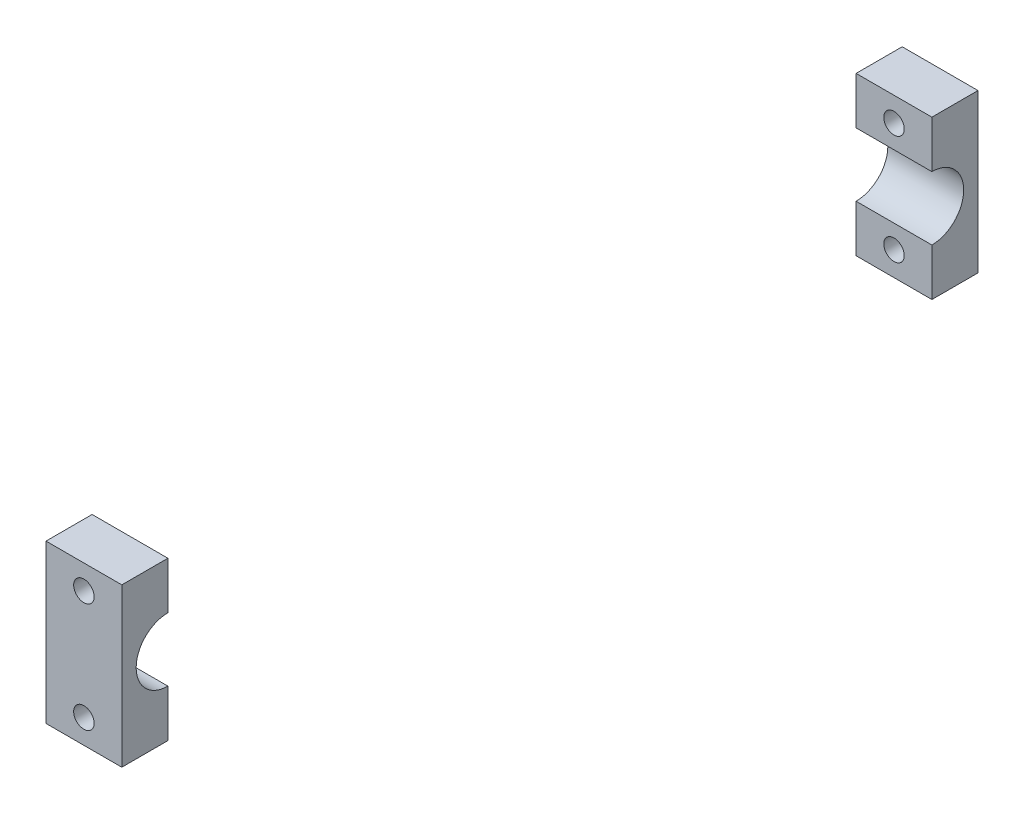
SolidWorks part; units mm, degrees
material "ABS"
ref_plane "Front Plane" through (0, 0, 0) normal (0, 0, 1) x (1, 0, 0)
ref_plane "Top Plane" through (0, 0, 0) normal (0, 1, 0) x (1, 0, 0)
ref_plane "Right Plane" through (0, 0, 0) normal (1, 0, 0) x (0, 0, -1)
sketch "Sketch2" plane through (0, 0, 0) normal (1, 0, 0) x (0, 0, -1)
  line L1 (-90, -4.5) -> (90, -4.5)
  line L2 (-90, -4.5) -> (-90, 4.5)
  line L3 (-90, 4.5) -> (90, 4.5)
  line L4 (90, -4.5) -> (90, 4.5)
  line L5 (-90, -4.5) -> (90, 4.5) construction
  line L6 (-90, 4.5) -> (90, -4.5) construction
  point P0 (0, 0)
  dimension "D1" = 9
  dimension "D2" = 180
extrude "Boss-Extrude1" add sketch "Sketch2" along normal blind 14.8
sketch "Sketch3" plane through (14.8, 0, 0) normal (1, 0, 0) x (0, 0, -1)
  line L0 (-90, -4.5) -> (90, -4.5) construction
  line L1 (-74.579, -4.5) -> (74.579, -4.5) construction
  line L7 (90, -4.5) -> (90, 4.5)
  line L8 (90, 4.5) -> (-90, 4.5)
  line L9 (-90, 4.5) -> (-90, -4.5)
  line L10 (-90, -4.5) -> (90, -4.5)
  line L11 (90, -4.5) -> (90, 4.5)
  line L12 (90, 4.5) -> (-90, 4.5)
  line L13 (-90, 4.5) -> (-90, -4.5)
  arc A0 (-68.379, -4.5) -> (-80.779, -4.5) centre (-74.579, -4.5) ccw
  arc A1 (80.779, -4.5) -> (68.379, -4.5) centre (74.579, -4.5) ccw
  point P10 (0, -4.5)
  dimension "D1" = 6.2
  dimension "D2" = 149.158
  dimension "D4" = 0
extrude "Bar Holes" [suppressed] cut sketch "Sketch3" against normal through all
sketch "Sketch6" [suppressed] plane through (0, 4.5, 0) normal (0, 1, 0) x (1, 0, 0)
  line L0 (7.4, 63.879) -> (7.4, -63.879) construction
  line L1 (14.8, 90) -> (0, 90) construction
  line L2 (14.8, -90) -> (0, -90) construction
  line L3 (0, -68.379) -> (14.8, -68.379) construction
  line L4 (0, -80.779) -> (14.8, -80.779) construction
  line L5 (-32.5661, 0) -> (77.6197, 0) construction
  circle A0 centre (7.4, 63.879) radius 2
  circle A1 centre (7.4, -63.879) radius 2
  circle A2 centre (7.4, -85.279) radius 2
  circle A3 centre (7.4, 85.279) radius 2
  circle A4 centre (7.4, -32.5) radius 3.5 construction
  circle A5 centre (7.4, 32.5) radius 3.5 construction
  point P4 (7.4, 0)
  point P8 (7.4, 90)
  point P17 (7.4, -90)
  dimension "D1" = 4
  dimension "D2" = 4
  dimension "D5" = 4
  dimension "D6" = 4
  dimension "D10" = 7
  dimension "D11" = 7
  dimension "D7" = 32.5
  dimension "D3" = 4.5
  dimension "D4" = 4.5
  dimension "D8" = 4.5
  dimension "D9" = 32.5
extrude "Bolt Holes" [suppressed] cut sketch "Sketch6" against normal through all
sketch "Sketch7" plane through (14.8, 0, 0) normal (1, 0, 0) x (0, 0, -1)
  line L0 (-90, -4.5) -> (90, -4.5) construction
  line L1 (-45, -4.5) -> (45, -4.5)
  line L2 (-45, -4.5) -> (-45, 0)
  line L3 (-45, 0) -> (45, 0)
  line L4 (45, -4.5) -> (45, 0)
  point P6 (0, 0)
  dimension "D1" = 90
extrude "Cut-Extrude1" cut sketch "Sketch7" against normal through all
fillet "Fillet1" radius 8 2 edges at (7.4, 0, -45) (7.4, 0, 45)
sketch "Sketch8" plane through (14.8, 0, 0) normal (1, 0, 0) x (0, 0, -1)
  line L0 (83.579, -39.5) -> (83.579, -54.92)
  line L1 (83.579, -4.5) -> (83.579, -39.5)
  line L2 (83.579, -39.5) -> (74.579, -39.5) construction
  line L3 (74.579, -33.3) -> (74.579, -4.5)
  line L4 (45, -4.5) -> (90, -4.5) construction
  line L5 (74.579, -4.5) -> (83.579, -4.5)
  line L6 (83.579, -54.92) -> (74.579, -54.92)
  line L7 (74.579, -54.92) -> (74.579, -45.7)
  line L8 (0, -7.0607) -> (0, -71.6637) construction
  line L9 (-74.579, -54.92) -> (-74.579, -45.7)
  line L10 (-83.579, -54.92) -> (-74.579, -54.92)
  line L11 (-83.579, -39.5) -> (-83.579, -54.92)
  line L12 (-83.579, -4.5) -> (-83.579, -39.5)
  line L13 (-74.579, -4.5) -> (-83.579, -4.5)
  line L14 (-74.579, -33.3) -> (-74.579, -4.5)
  arc A0 (74.579, -45.7) -> (74.579, -33.3) centre (74.579, -39.5) ccw
  arc A1 (-74.579, -45.7) -> (-74.579, -33.3) centre (-74.579, -39.5) cw
  dimension "D1" = 15.42
  dimension "D2" = 35
  dimension "D3" = 9
extrude "Boss-Extrude2" add sketch "Sketch8" against normal blind 14.8
sketch "Sketch11" plane through (0, 0, 74.579) normal (0, 0, -1) x (-1, 0, 0)
  line L0 (-7.4, -33.3) -> (-7.4, -28.8) construction
  line L1 (0, -33.3) -> (-14.8, -33.3) construction
  line L2 (-7.4, -33.3) -> (-7.4, -45.7) construction
  line L3 (0, -45.7) -> (-14.8, -45.7) construction
  line L4 (-7.4, -39.5) -> (0, -39.5) construction
  circle A1 centre (-7.4, -28.8) radius 2
  circle A2 centre (-7.4, -50.2) radius 2
  dimension "D1" = 4.5
extrude "Cut-Extrude2" cut sketch "Sketch11" along normal through all both and the other way through all
sketch "Sketch12" plane through (0, 0, 0) normal (-1, 0, 0) x (0, 0, 1)
  line L4 (96.9862, 8.7415) -> (-95.1532, 8.7415)
  line L5 (96.9862, 8.7415) -> (96.9862, -4.5)
  line L9 (-95.1532, 8.7415) -> (-95.1532, -16.0389)
  line L11 (96.9862, -16.0389) -> (96.9862, -4.5)
  line L12 (74.579, -33.3) -> (74.579, -24.08) construction
  line L13 (74.579, -33.3) -> (74.579, -4.5) construction
  line L15 (74.579, -24.08) -> (96.9862, -24.08)
  line L16 (96.9862, -24.08) -> (96.9862, -16.0389)
  line L17 (74.579, -24.08) -> (-95.1532, -24.08)
  line L18 (-95.1532, -24.08) -> (-95.1532, -16.0389)
  dimension "D1" = 9.22
extrude "Cut-Extrude3" cut sketch "Sketch12" against normal through all both
